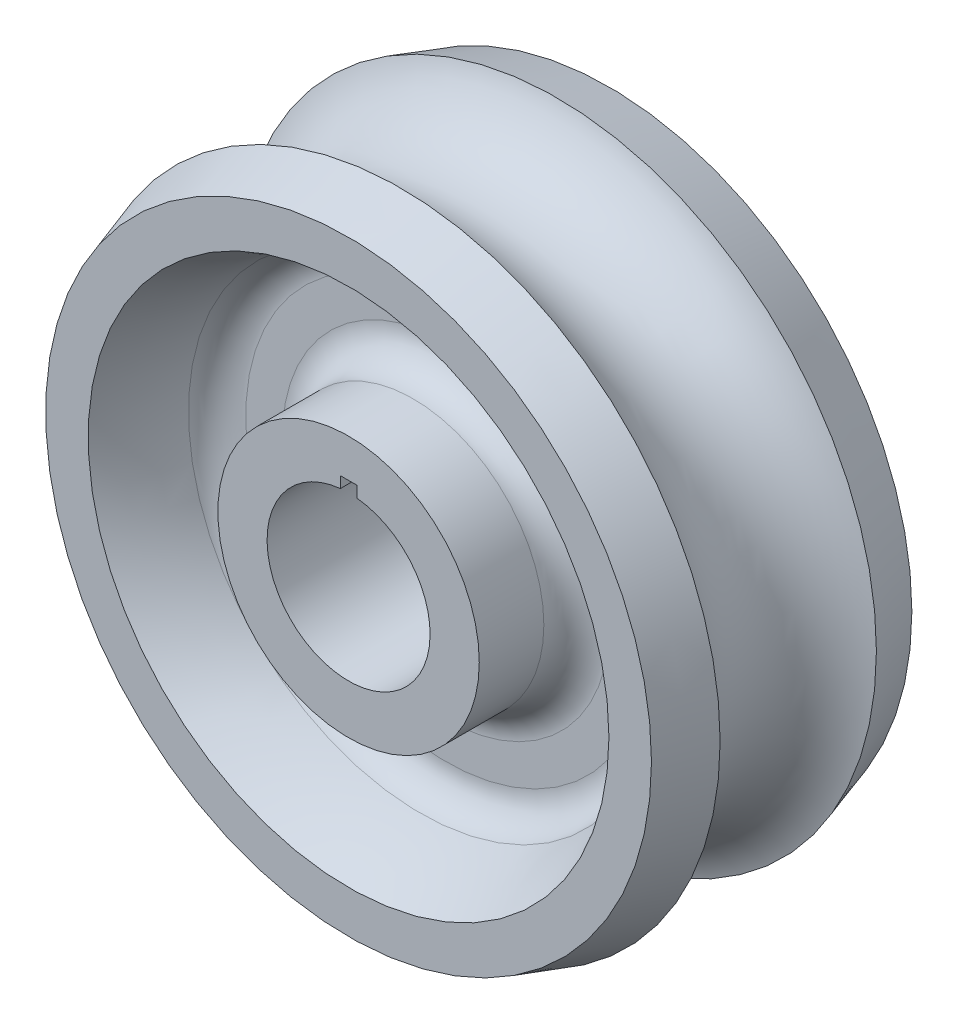
SolidWorks part; units mm, degrees
material "PW20:29:Sc:0:"
ref_plane "Front" through (0, 0, 0) normal (0, 0, 1) x (1, 0, 0)
ref_plane "Top" through (0, 0, 0) normal (0, 1, 0) x (1, 0, 0)
ref_plane "Right" through (0, 0, 0) normal (1, 0, 0) x (0, 0, -1)
sketch "Sketch1" plane through (0, 0, 0) normal (1, 0, 0) x (0, 0, -1)
  line L0 (0, 0) -> (159.8623, 0) construction
  line L1 (0, 0) -> (0, 93.2897) construction
  line L2 (-12.7, 7.95) -> (12.7, 7.95)
  line L3 (12.7, 7.95) -> (12.7, 12.75)
  line L4 (12.7, 12.75) -> (6.4, 12.75)
  line L5 (3.2, 15.95) -> (3.2, 19.5223)
  line L6 (12.7, 25.4) -> (12.7, 29.55)
  line L7 (12.7, 29.55) -> (7.6218, 31.1694)
  line L8 (-12.7, 29.55) -> (-7.6218, 31.1694)
  line L9 (-12.7, 25.4) -> (-12.7, 29.55)
  line L10 (-3.2, 15.95) -> (-3.2, 19.5223)
  line L11 (-12.7, 12.75) -> (-6.4, 12.75)
  line L12 (-12.7, 7.95) -> (-12.7, 12.75)
  arc A0 (6.4, 12.75) -> (3.2, 15.95) centre (6.4, 15.95) cw
  arc A1 (3.2, 19.5223) -> (5.6839, 22.6412) centre (6.4, 19.5223) cw
  arc A2 (5.6839, 22.6412) -> (12.7, 25.4) centre (0, 47.397) ccw
  arc A3 (7.6218, 31.1694) -> (-7.6218, 31.1694) centre (0, 33.6) cw
  arc A4 (-5.6839, 22.6412) -> (-12.7, 25.4) centre (0, 47.397) cw
  arc A5 (-3.2, 19.5223) -> (-5.6839, 22.6412) centre (-6.4, 19.5223) ccw
  arc A6 (-6.4, 12.75) -> (-3.2, 15.95) centre (-6.4, 15.95) ccw
  point P29 (0, 7.95)
  dimension "D1" = 25.4
  dimension "D2" = 3.2
  dimension "D4" = 8
  dimension "D9" = 25.4
  dimension "D3" = 50.8
  dimension "D5" = 6.4
  dimension "D6" = 4.8
  dimension "D7" = 15.9
  dimension "D8" = 21.6
  dimension "D10" = 67.2
revolve "Base-Revolve" add sketch "Sketch1" angle 360 about L0
sketch "Sketch2" plane through (0, 0, 12.7) normal (0, 0, 1) x (1, 0, 0)
  line L0 (0, 0) -> (0, 10.5711) construction
  line L1 (-0.8, 7.9096) -> (-0.8, 9)
  line L2 (0.8, 7.9096) -> (0.8, 9)
  line L3 (-0.8, 9) -> (0.8, 9)
  circle A0 centre (0, 0) radius 7.95 construction
  arc A1 (0.8, 7.9096) -> (-0.8, 7.9096) centre (0, 0) ccw
  dimension "D1" = 1.6
  dimension "D2" = 9
extrude "Cut-Extrude1" cut sketch "Sketch2" against normal through all
ref_axis "Worm CL" through (0, 0, 50) along (0, 0, -1)
